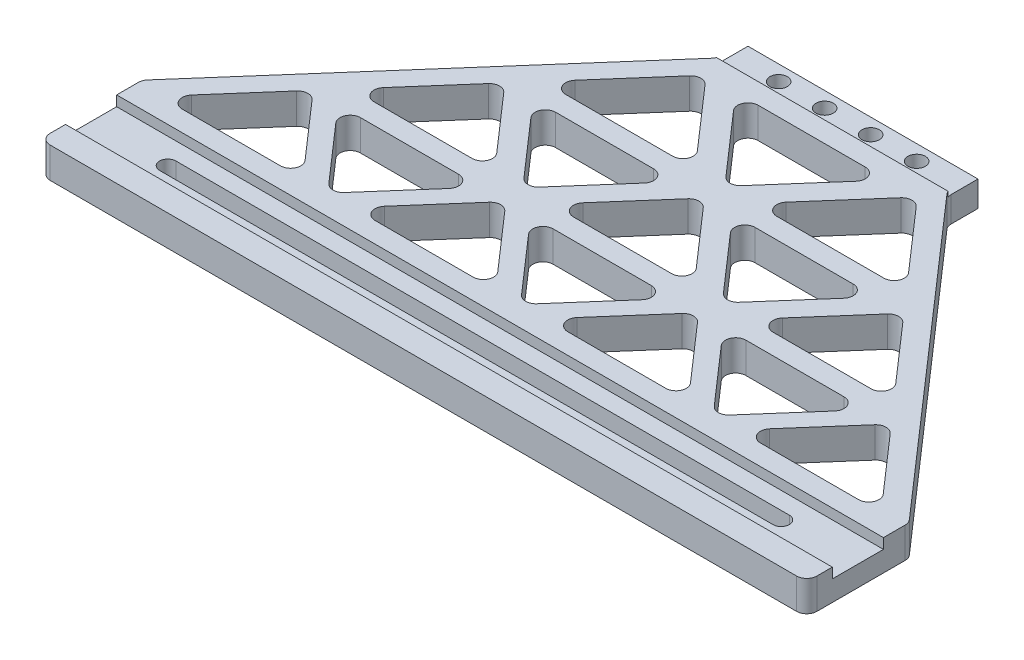
SolidWorks part; units mm, degrees
material "Сплав 2024"
ref_plane "Спереди" through (0, 0, 0) normal (0, 0, 1) x (1, 0, 0)
ref_plane "Сверху" through (0, 0, 0) normal (0, 1, 0) x (1, 0, 0)
ref_plane "Справа" through (0, 0, 0) normal (1, 0, 0) x (0, 0, -1)
sketch "Эскиз1" plane through (0, 0, 0) normal (0, 1, 0) x (1, 0, 0)
  line L0 (-22.5, 0) -> (22.5, 0) construction
  line L1 (-22.5, 3) -> (22.5, 3)
  line L2 (-22.5, 3) -> (-22.5, -3)
  line L3 (-22.5, -3) -> (22.5, -3) construction
  line L4 (22.5, 3) -> (22.5, -3)
  line L5 (-22.5, 3) -> (22.5, -3) construction
  line L6 (-22.5, -3) -> (22.5, 3) construction
  line L7 (0, 3) -> (0, -3) construction
  line L8 (-22.5, -3) -> (-75, -63)
  line L9 (-75, -63) -> (-75, -83)
  line L10 (-75, -83) -> (75, -83)
  line L11 (75, -83) -> (75, -63)
  line L12 (75, -63) -> (22.5, -3)
  line L13 (0, -3) -> (0, -163) construction
  line L14 (75, -63) -> (-75, -63) construction
  line L15 (-13.5, 3) -> (-13.5, -3) construction
  line L16 (-4.5, 3) -> (-4.5, -3) construction
  line L17 (4.5, 3) -> (4.5, -3) construction
  line L18 (13.5, 3) -> (13.5, -3) construction
  point P0 (0, 0)
  point P10 (0, -83)
  dimension "D1" = 45
  dimension "D2" = 6
  dimension "D3" = 150
  dimension "D4" = 80
  dimension "D5" = 20
  dimension "D6" = 9
  dimension "D7" = 9
  dimension "D8" = 9
  dimension "D9" = 9
extrude "Бобышка-Вытянуть1" add sketch "Эскиз1" along normal blind 6
sketch "Эскиз2" plane through (0, 6, 0) normal (0, 1, 0) x (1, 0, 0)
  line L0 (75, -83) -> (75, -63) construction
  line L1 (-75, -78) -> (75, -78)
  line L2 (-75, -78) -> (-75, -68)
  line L3 (-75, -68) -> (75, -68)
  line L4 (75, -78) -> (75, -68)
  line L5 (-75, -83) -> (75, -83) construction
  dimension "D1" = 10
  dimension "D2" = 5
extrude "Вырез-Вытянуть1" cut sketch "Эскиз2" against normal blind 2
fillet "Скругление3" radius 2 2 edges at (22.5, 3, 3) (-22.5, 3, 3)
sketch "Эскиз3" plane through (0, 6, 0) normal (0, 1, 0) x (1, 0, 0)
  line L0 (22.5, 3) -> (-22.5, 3) construction
  line L1 (-23.5, 3) -> (23.5, 3)
  line L2 (-23.5, 3) -> (-23.5, -3)
  line L3 (-23.5, -3) -> (23.5, -3)
  line L4 (23.5, 3) -> (23.5, -3)
  line L5 (-22.5, 3) -> (-22.5, -2.2485) construction
  dimension "D1" = 6
  dimension "D2" = 47
  dimension "D3" = 1
extrude "Вырез-Вытянуть2" cut sketch "Эскиз3" against normal blind 1
hole_wizard "Отверстие с зазором M31" positions "Эскиз8" profile "Эскиз7" hole size "M3" standard "Ansi Metric" end condition through all
sketch "Эскиз8" plane through (0, 0, 0) normal (0, -1, 0) x (-1, 0, 0)
  line L0 (-13.5, 3) -> (-13.5, -3) construction
  line L1 (-4.5, 3) -> (-4.5, -3) construction
  line L2 (4.5, 3) -> (4.5, -3) construction
  line L3 (13.5, 3) -> (13.5, -3) construction
  point P0 (-13.5, 0)
  point P4 (-4.5, 0)
  point P8 (4.5, 0)
  point P12 (13.5, 0)
sketch "Эскиз7" plane through (13.5, 0, 0) normal (1, 0, 0) x (0, 0, -1)
  line L0 (0, 0) -> (0, 6)
  line L1 (0, 6) -> (1.7, 6)
  line L2 (1.7, 6) -> (1.7, 0)
  line L5 (1.7, 0) -> (0, 0)
  line L11 (0, -6.35) -> (0, 107.95) construction
  dimension "Диаметр сквозного отверстия" = 3.4
  dimension "Глубина сквозного отверстия" = 6
sketch "Эскиз9" plane through (0, 4, 0) normal (0, 1, 0) x (1, 0, 0)
  line L0 (-60, -73) -> (60, -73) construction
  line L1 (-60, -71.4) -> (60, -71.4)
  line L2 (-60, -74.6) -> (60, -74.6)
  line L3 (0, -68) -> (0, -78) construction
  line L4 (75, -68) -> (-75, -68) construction
  line L5 (-75, -78) -> (75, -78) construction
  arc A0 (-60, -71.4) -> (-60, -74.6) centre (-60, -73) ccw
  arc A1 (60, -74.6) -> (60, -71.4) centre (60, -73) ccw
  point P2 (0, -73)
  dimension "D1" = 1.6
  dimension "D2" = 120
extrude "Вырез-Вытянуть3" cut sketch "Эскиз9" against normal through all
sketch "Эскиз10" plane through (0, 6, 0) normal (0, 1, 0) x (1, 0, 0)
  line L0 (-2.3315, 13.9753) -> (-85.5296, -81.1082) construction
  line L1 (-1.4219, 18.2649) -> (84.9093, -80.3992) construction
  line L2 (-75, -64) -> (75, -64) construction
  line L3 (-22.9948, -3.5655) -> (-75, -63) construction
  line L4 (75, -63) -> (22.9948, -3.5655) construction
  line L5 (75, -68) -> (-75, -68) construction
  line L6 (-36.0661, -7) -> (36.2465, -7) construction
  line L7 (-22.6465, -3) -> (22.6465, -3) construction
  line L8 (-66.3605, -48) -> (66.7235, -48) construction
  line L9 (-59.8686, -44) -> (61.8546, -44) construction
  line L10 (-43.099, -28) -> (53.3779, -28) construction
  line L11 (36.2465, -24) -> (-41.2957, -24) construction
  line L12 (-70.5599, -64) -> (-56.5599, -48)
  line L13 (-56.5599, -48) -> (-42.5599, -64)
  line L14 (-42.5599, -64) -> (-70.5599, -64)
  line L15 (-51.7099, -48) -> (-37.7099, -64)
  line L16 (-37.7099, -64) -> (-23.7099, -48)
  line L17 (-23.7099, -48) -> (-51.7099, -48)
  line L18 (-18.8599, -48) -> (-32.8599, -64)
  line L19 (-32.8599, -64) -> (-4.8599, -64)
  line L20 (-4.8599, -64) -> (-18.8599, -48)
  line L21 (-14.0099, -48) -> (-0.0099, -64)
  line L22 (-0.0099, -64) -> (13.9901, -48)
  line L23 (13.9901, -48) -> (-14.0099, -48)
  line L24 (18.8401, -48) -> (4.8401, -64)
  line L25 (4.8401, -64) -> (32.8401, -64)
  line L26 (32.8401, -64) -> (18.8401, -48)
  line L27 (23.6901, -48) -> (37.6901, -64)
  line L28 (37.6901, -64) -> (51.6901, -48)
  line L29 (51.6901, -48) -> (23.6901, -48)
  line L31 (42.5401, -64) -> (70.5401, -64)
  line L32 (70.5401, -64) -> (56.5401, -48)
  line L33 (56.5401, -48) -> (42.5401, -64)
  line L34 (-75, -63) -> (-75, -68) construction
  line L35 (75, -68) -> (75, -63) construction
  line L36 (-53.0599, -44) -> (-39.0599, -28)
  line L37 (-39.0599, -28) -> (-25.0599, -44)
  line L38 (-25.0599, -44) -> (-53.0599, -44)
  line L39 (-33.5455, -28) -> (-19.5455, -44)
  line L40 (-19.5455, -44) -> (-5.5455, -28)
  line L41 (-5.5455, -28) -> (-33.5455, -28)
  line L42 (-0.0312, -28) -> (-14.0312, -44)
  line L43 (-14.0312, -44) -> (13.9688, -44)
  line L44 (13.9688, -44) -> (-0.0312, -28)
  line L45 (5.4832, -28) -> (19.4832, -44)
  line L46 (19.4832, -44) -> (33.4832, -28)
  line L47 (33.4832, -28) -> (5.4832, -28)
  line L48 (24.9976, -44) -> (38.9976, -28)
  line L49 (38.9976, -28) -> (52.9976, -44)
  line L50 (52.9976, -44) -> (24.9976, -44)
  line L51 (-35.5599, -24) -> (-20.6849, -7)
  line L52 (-20.6849, -7) -> (-5.8099, -24)
  line L53 (-5.8099, -24) -> (-35.5599, -24)
  line L54 (-14.9048, -7) -> (-0.0298, -24)
  line L55 (-0.0298, -24) -> (14.8452, -7)
  line L56 (14.8452, -7) -> (-14.9048, -7)
  line L57 (20.6254, -7) -> (5.7504, -24)
  line L58 (5.7504, -24) -> (35.5004, -24)
  line L59 (35.5004, -24) -> (20.6254, -7)
  dimension "D1" = 4
  dimension "D2" = 4
  dimension "D3" = 4
  dimension "D4" = 4
  dimension "D5" = 4
  dimension "D6" = 4
  dimension "D7" = 48.814
  dimension "D8" = 48.814
  dimension "D9" = 57
  dimension "D10" = 16
  dimension "D11" = 16
  dimension "D12" = 82.372
  dimension "D13" = 82.372
  dimension "D14" = 82.372
  dimension "D15" = 82.372
  dimension "D16" = 3.65
  dimension "D17" = 3.65
  dimension "D18" = 82.372
  dimension "D19" = 82.372
  dimension "D20" = 3.65
  dimension "D21" = 3.65
  dimension "D22" = 3.65
  dimension "D23" = 3.65
  dimension "D24" = 82.372
  dimension "D25" = 4.15
  dimension "D26" = 4.15
  dimension "D27" = 4.15
  dimension "D28" = 82.372
  dimension "D29" = 82.372
  dimension "D30" = 82.372
  dimension "D31" = 82.372
  dimension "D32" = 4.15
  dimension "D33" = 82.372
  dimension "D34" = 82.372
  dimension "D35" = 82.372
  dimension "D36" = 82.372
  dimension "D37" = 4.35
  dimension "D38" = 4.35
extrude "Вырез-Вытянуть4" cut sketch "Эскиз10" against normal up to next
fillet "Скругление1" radius 2 49 edges at (18.8401, 3, 48) (23.6901, 3, 48) (-14.0099, 3, 48) (-51.7099, 3, 48) (-33.5455, 3, 28) (5.4832, 3, 28) (5.7504, 3, 24) (24.9976, 3, 44) (4.8401, 3, 64) (-32.8599, 3, 64) (-70.5599, 3, 64) (-14.0312, 3, 44) (-53.0599, 3, 44) (-35.5599, 3, 24) (-42.5599, 3, 64) (-25.0599, 3, 44) (-4.8599, 3, 64) (35.5004, 3, 24) (52.9976, 3, 44) (70.5401, 3, 64) (32.8401, 3, 64) (13.9688, 3, 44) (-5.8099, 3, 24) (-0.0298, 3, 24) (-37.7099, 3, 64) (-0.0099, 3, 64) (19.4832, 3, 44) (37.6901, 3, 64) (56.5401, 3, 48) (38.9976, 3, 28) (-0.0312, 3, 28) (-18.8599, 3, 48) (-56.5599, 3, 48) (-39.0599, 3, 28) (-20.6849, 3, 7) (20.6254, 3, 7) (-23.7099, 3, 48) (13.9901, 3, 48) (-5.5455, 3, 28) (51.6901, 3, 48) (33.4832, 3, 28) (14.8452, 3, 7) (-75, 3, 63) (-75, 3, 83) (75, 3, 83) (75, 3, 63) (-19.5455, 3, 44) (42.5401, 3, 64) (-14.9048, 3, 7)
fillet "Скругление2" [suppressed] radius 2
equation "\"D6@Эскиз1\"=\"D1@Эскиз1\"/5"
equation "\"D7@Эскиз1\"=\"D6@Эскиз1\""
equation "\"D8@Эскиз1\"=\"D6@Эскиз1\""
equation "\"D9@Эскиз1\"=\"D6@Эскиз1\""
equation "\"D13@Эскиз10\"=\"D12@Эскиз10\""
equation "\"D14@Эскиз10\"=\"D12@Эскиз10\""
equation "\"D15@Эскиз10\"=\"D12@Эскиз10\""
equation "\"D18@Эскиз10\"=\"D12@Эскиз10\""
equation "\"D19@Эскиз10\"=\"D12@Эскиз10\""
equation "\"D24@Эскиз10\"=\"D12@Эскиз10\""
equation "\"D17@Эскиз10\"=\"D16@Эскиз10\""
equation "\"D23@Эскиз10\"=\"D16@Эскиз10\""
equation "\"D22@Эскиз10\"=\"D16@Эскиз10\""
equation "\"D20@Эскиз10\"=\"D16@Эскиз10\""
equation "\"D21@Эскиз10\"=\"D16@Эскиз10\""
equation "\"D28@Эскиз10\"=\"D12@Эскиз10\""
equation "\"D29@Эскиз10\"=\"D28@Эскиз10\""
equation "\"D30@Эскиз10\"=\"D28@Эскиз10\""
equation "\"D31@Эскиз10\"=\"D28@Эскиз10\""
equation "\"D32@Эскиз10\"=\"D25@Эскиз10\""
equation "\"D26@Эскиз10\"=\"D25@Эскиз10\""
equation "\"D27@Эскиз10\"=\"D25@Эскиз10\""
equation "\"D33@Эскиз10\"=\"D28@Эскиз10\""
equation "\"D34@Эскиз10\"=\"D12@Эскиз10\""
equation "\"D35@Эскиз10\"=\"D34@Эскиз10\""
equation "\"D36@Эскиз10\"=\"D34@Эскиз10\""
equation "\"D38@Эскиз10\"=\"D37@Эскиз10\""
